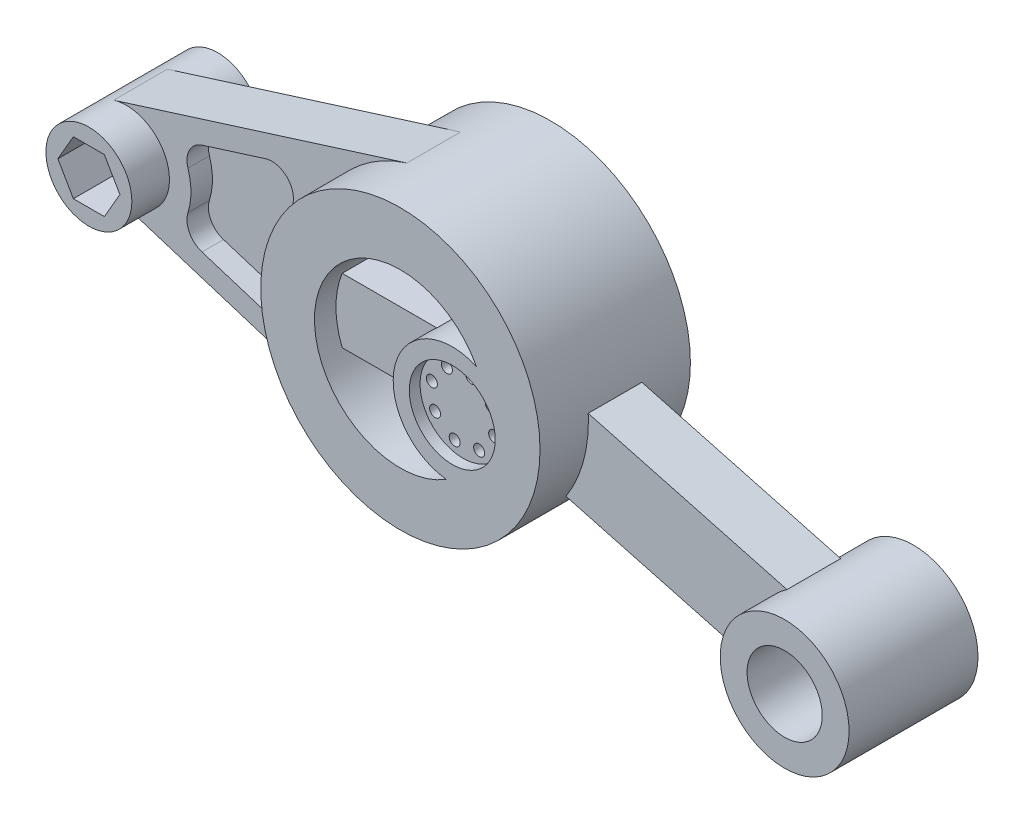
SolidWorks part; units mm, degrees
material "Copper"
ref_plane "Front Plane" through (0, 0, 0) normal (0, 0, 1) x (1, 0, 0)
ref_plane "Top Plane" through (0, 0, 0) normal (0, 1, 0) x (1, 0, 0)
ref_plane "Right Plane" through (0, 0, 0) normal (1, 0, 0) x (0, 0, -1)
ref_plane "CENTRE_Plane" through (150, 0, 0) normal (1, 0, 0) x (0, 0, -1)
ref_axis "CENTRE_Plane_Axis" through (150, 0, 33) along (0, 0, -1)
ref_plane "CENTRE_RIGHT_Plane" through (139.9519, -37.5, 0) normal (0.9659, -0.2588, 0) x (0, 0, -1)
ref_plane "RIGHT_Plane" through (313.8186, -84.0874, 0) normal (0.9659, -0.2588, 0) x (0, 0, -1)
sketch "Sketch1" plane through (0, 0, 0) normal (0, 0, 1) x (1, 0, 0)
  line L0 (-6, 19.0788) -> (130.5, 62.006)
  line L1 (-6, -19.0788) -> (130.5, -62.006)
  arc A0 (-6, 19.0788) -> (-6, -19.0788) centre (0, 0) ccw
  arc A1 (130.5, -62.006) -> (130.5, 62.006) centre (150, 0) ccw
  dimension "D1" = 40
  dimension "D2" = 130
extrude "LEFT_ARM" add sketch "Sketch1" along normal mid plane 25
sketch "Sketch2" plane through (0, 0, 0) normal (0, 0, 1) x (1, 0, 0)
  circle A0 centre (0, 0) radius 20
  dimension "D1" = 40
extrude "LEFT_Boss" add sketch "Sketch2" along normal mid plane 60
sketch "Sketch4" plane through (0, 0, 30) normal (0, 0, 1) x (1, 0, 0)
  line L0 (38.5, 0) -> (-38.5, 0) construction
  line L1 (14.4338, 0) -> (7.2169, 12.5)
  line L2 (7.2169, 12.5) -> (-7.2169, 12.5)
  line L3 (-7.2169, 12.5) -> (-14.4338, 0)
  line L4 (-14.4338, 0) -> (-7.2169, -12.5)
  line L5 (-7.2169, -12.5) -> (7.2169, -12.5)
  line L6 (7.2169, -12.5) -> (14.4338, 0)
  circle A0 centre (0, 0) radius 12.5 construction
  dimension "D1" = 25
extrude "LEFT_Hex" cut sketch "Sketch4" against normal through all both and the other way through all
sketch "Sketch3" plane through (0, 0, 0) normal (0, 0, 1) x (1, 0, 0)
  circle A0 centre (150, 0) radius 65
  dimension "D1" = 130
extrude "CENTRE_Boss" add sketch "Sketch3" along normal mid plane 70
sketch "Sketch5" plane through (139.9519, -37.5, 0) normal (0.9659, -0.2588, 0) x (0, 0, -1)
  line L0 (-33, 38.8229) -> (33, 38.8229) construction
  line L1 (-12.5, 18.8229) -> (12.5, 18.8229)
  line L2 (-12.5, 18.8229) -> (-12.5, 58.8229)
  line L3 (-12.5, 58.8229) -> (12.5, 58.8229)
  line L4 (12.5, 18.8229) -> (12.5, 58.8229)
  line L5 (-12.5, 18.8229) -> (12.5, 58.8229) construction
  line L6 (-12.5, 58.8229) -> (12.5, 18.8229) construction
  line L7 (0, 77.8731) -> (0, -77.8731) construction
  point P0 (0, 38.8229)
  dimension "D1" = 25
  dimension "D2" = 40
extrude "RIGHT_ARM" add sketch "Sketch5" along normal up to surface (180 mm away) up to plane "RIGHT_Plane"
sketch "RIGHT_ARM_CL" plane through (0, 0, 0) normal (0, 0, 1) x (1, 0, 0)
  line L0 (150, 0) -> (323.8666, -46.5874) construction
  line L1 (298.5122, -141.2116) -> (329.1249, -26.9633) construction
sketch "Sketch7" plane through (0, 0, 0) normal (0, 0, 1) x (1, 0, 0)
  circle A0 centre (323.8666, -46.5874) radius 30
  dimension "D1" = 60
extrude "RIGHT_Boss" add sketch "Sketch7" along normal mid plane 60
sketch "Sketch8" plane through (0, 0, 30) normal (0, 0, 1) x (1, 0, 0)
  circle A0 centre (323.8666, -46.5874) radius 17.5
  dimension "D1" = 35
extrude "RIGHT_Boss_Hole" cut sketch "Sketch8" against normal through all
sketch "Sketch9" plane through (0, 0, 35) normal (0, 0, 1) x (1, 0, 0)
  circle A0 centre (150, 0) radius 40
  dimension "D1" = 80
extrude "CENTRE_Hole" cut sketch "Sketch9" against normal through all
sketch "Sketch10" plane through (0, 0, 0) normal (0, 0, 1) x (1, 0, 0)
  line L0 (150, 0) -> (323.8666, -46.5874) construction
  line L1 (124.2934, -95.9385) -> (155.6105, 20.9385) construction
  circle A0 centre (174.1481, -6.4705) radius 27.5
  dimension "D1" = 55
  dimension "D2" = 25
extrude "CENTRE_Blob" add sketch "Sketch10" along normal mid plane 70
sketch "Sketch11" plane through (150, 0, 0) normal (1, 0, 0) x (0, 0, -1)
  line L1 (-25, -15) -> (25, -15)
  line L2 (-25, -15) -> (-25, 15)
  line L3 (-25, 15) -> (25, 15)
  line L4 (25, -15) -> (25, 15)
  line L5 (-25, -15) -> (25, 15) construction
  line L6 (-25, 15) -> (25, -15) construction
  point P0 (0, 0)
  dimension "D1" = 50
  dimension "D2" = 30
extrude "CENTRE_Beam" add sketch "Sketch11" along normal up to next and the other way up to next
sketch "Sketch12" plane through (0, 0, 35) normal (0, 0, 1) x (1, 0, 0)
  circle A0 centre (174.1481, -6.4705) radius 20
  dimension "D1" = 40
extrude "Cut-Extrude4" cut sketch "Sketch12" against normal blind 5
hole_wizard "1/4-20 Tapped Hole1" positions "Sketch13" profile "Sketch14" tap size "1/4-20" standard "ANSI Inch" end condition up to next
sketch "Sketch13" plane through (0, 0, 30) normal (0, 0, 1) x (1, 0, 0)
  line L0 (150, 0) -> (323.8666, -46.5874) construction
  circle A0 centre (174.1481, -6.4705) radius 20 construction
  point P0 (159.6593, -2.5882)
  dimension "D1" = 15
sketch "Sketch14" plane through (159.6593, -2.5882, 30) normal (1, 0, 0) x (0, -1, 0)
  line L0 (0, 0) -> (0, 65)
  line L1 (0, 65) -> (2.5527, 65)
  line L2 (2.5527, 65) -> (2.5527, 0)
  line L5 (2.5527, 0) -> (0, 0)
  line L11 (0, -6.35) -> (0, 107.95) construction
  dimension "Thru Tap Drill Dia." = 5.1054
  dimension "Thru Tap Drill Depth" = 65
cosmetic thread "Hole Thread1" parameters "D2"=6.35
pattern_circular "CirPattern1" count 8 over 360 about axis through (174.1481, -6.4705, 30) along (0, 0, 1) of "1/4-20 Tapped Hole1"
cosmetic thread "Hole Thread2" parameters "D2"=6.35
cosmetic thread "Hole Thread3" parameters "D2"=6.35
cosmetic thread "Hole Thread4" parameters "D2"=6.35
cosmetic thread "Hole Thread5" parameters "D2"=6.35
cosmetic thread "Hole Thread6" parameters "D2"=6.35
cosmetic thread "Hole Thread7" parameters "D2"=6.35
cosmetic thread "Hole Thread8" parameters "D2"=6.35
mirror "Mirror1" about plane through (0, 0, 0) normal (0, 0, 1) of "Cut-Extrude4"
sketch "Sketch15" plane through (0, 0, 12.5) normal (0, 0, 1) x (1, 0, 0)
  line L24 (84.8585, 37.1696) -> (-3, 9.5394)
  line L25 (-3, -9.5394) -> (84.8585, -37.1696)
  line L26 (84.8585, 37.1696) -> (23.9815, 18.0247)
  line L27 (23.9815, -18.0247) -> (84.8585, -37.1696)
  arc A12 (84.8585, 37.1696) -> (84.8585, -37.1696) centre (150, 0) ccw
  arc A13 (84.8585, 37.1696) -> (84.8585, -37.1696) centre (150, 0) ccw
  arc A23 (-9, -28.6182) -> (-9, 28.6182) centre (0, 0) ccw
  arc A24 (23.9815, -18.0247) -> (23.9815, 18.0247) centre (0, 0) ccw
  dimension "D1" = 10
  dimension "D2" = 10
extrude "Cut_OUT" cut sketch "Sketch15" against normal blind 10
fillet "Fillet1" radius 10 4 edges at (84.8585, 37.1696, 7.5) (84.8585, -37.1696, 7.5) (23.9815, -18.0247, 7.5) (23.9815, 18.0247, 7.5)
mirror "Mirror2" about plane through (0, 0, 0) normal (0, 0, 1) of "Fillet1", "Cut_OUT"
sketch "Sketch16" plane through (0, 0, 0) normal (0, 0, 1) x (1, 0, 0)
  line L0 (322.0549, -53.3489) -> (325.6784, -39.8259)
  line L1 (298.5122, -141.2116) -> (329.1249, -26.9633) construction
  line L2 (325.6784, -39.8259) -> (297.8597, -32.372)
  line L3 (297.8597, -32.372) -> (294.2363, -45.8949)
  line L4 (294.2363, -45.8949) -> (322.0549, -53.3489)
  circle A0 centre (323.8666, -46.5874) radius 17.5 construction
  point P4 (323.8666, -46.5874)
  dimension "D1" = 14
  dimension "D2" = 28.8
extrude "KEYWAY" [suppressed] cut sketch "Sketch16" against normal through all both and the other way through all
mirror "Mirror3" [suppressed] about plane through (313.8186, -84.0874, 0) normal (0.9659, -0.2588, 0)
equation "\"D1@Sketch2\"=\"D1@Sketch1\""
equation "\"D1@Sketch3\"=\"D2@Sketch1\""
equation "\"D2@Sketch16\"=25+3.8"
